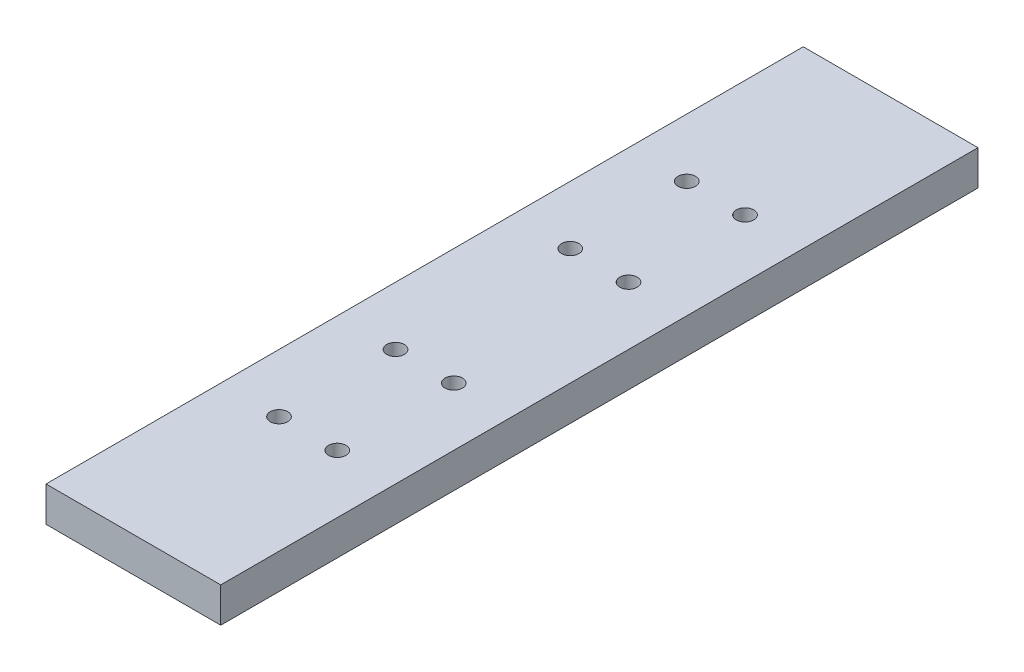
SolidWorks part; units mm, degrees
ref_plane "Front Plane" through (0, 0, 0) normal (0, 0, 1) x (1, 0, 0)
ref_plane "Top Plane" through (0, 0, 0) normal (0, 1, 0) x (1, 0, 0)
ref_plane "Right Plane" through (0, 0, 0) normal (1, 0, 0) x (0, 0, -1)
sketch "Sketch2" plane through (0, 0, 0) normal (0, 0, 1) x (1, 0, 0)
  line L1 (-15, -3) -> (15, -3)
  line L2 (-15, -3) -> (-15, 3)
  line L3 (-15, 3) -> (15, 3)
  line L4 (15, -3) -> (15, 3)
  line L5 (0, 3) -> (0, -3) construction
  line L6 (-15, 0) -> (15, 0) construction
  point P0 (0, 0)
  dimension "D1" = 6
  dimension "D2" = 30
extrude "Boss-Extrude1" add sketch "Sketch2" along normal blind 130
sketch "Sketch3" plane through (0, 3, 0) normal (0, 1, 0) x (1, 0, 0)
  line L0 (-15, -65) -> (15, -65) construction
  line L1 (-15, -130) -> (-15, 0) construction
  line L2 (15, -130) -> (15, 0) construction
  line L3 (-5, -130) -> (-5, -100) construction
  line L4 (15, -130) -> (-15, -130) construction
  line L5 (-5, -100) -> (-15, -100) construction
  circle A0 centre (-5, -100) radius 1.5
  circle A1 centre (5, -100) radius 1.5
  circle A2 centre (5, -80) radius 1.5
  circle A3 centre (-5, -80) radius 1.5
  circle A4 centre (-5, -50) radius 1.5
  circle A5 centre (5, -50) radius 1.5
  circle A6 centre (5, -30) radius 1.5
  circle A7 centre (-5, -30) radius 1.5
  dimension "D3" = 3
  dimension "D4" = 2
  dimension "D5" = 2
  dimension "D1" = 30
  dimension "D2" = 10
extrude "Cut-Extrude3" cut sketch "Sketch3" against normal through all
